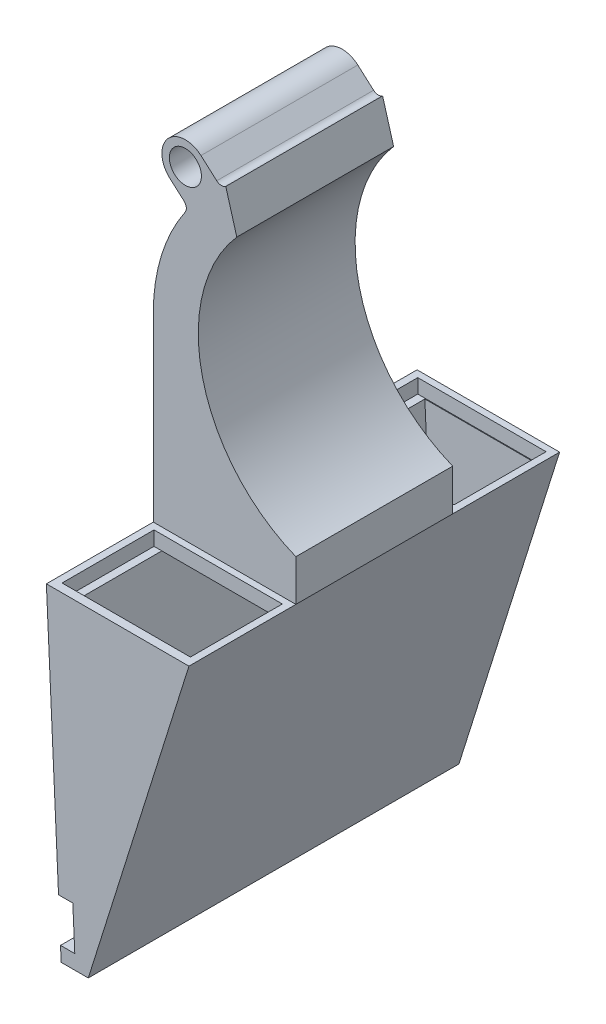
SolidWorks part; units mm, degrees
ref_plane "Front Plane" through (0, 0, 0) normal (0, 0, 1) x (1, 0, 0)
ref_plane "Top Plane" through (0, 0, 0) normal (0, 1, 0) x (1, 0, 0)
ref_plane "Right Plane" through (0, 0, 0) normal (1, 0, 0) x (0, 0, -1)
sketch "Sketch4" plane through (0, -25.4, 0) normal (0, -1, 0) x (1, 0, 0)
  line L1 (-8.5, -1.2) -> (-26.5, -1.2)
  line L2 (-8.5, -1.2) -> (-8.5, -14.1)
  line L3 (-8.5, -14.1) -> (-26.5, -14.1)
  line L4 (-26.5, -1.2) -> (-26.5, -14.1)
  line L5 (-8.5, -1.2) -> (-26.5, -14.1) construction
  line L6 (-8.5, -14.1) -> (-26.5, -1.2) construction
  line L7 (-26.5, -38.2) -> (-8.5, -38.2)
  line L8 (-26.5, -38.2) -> (-26.5, -51.1)
  line L9 (-26.5, -51.1) -> (-8.5, -51.1)
  line L10 (-8.5, -38.2) -> (-8.5, -51.1)
  line L11 (-26.5, -38.2) -> (-8.5, -51.1) construction
  line L12 (-26.5, -51.1) -> (-8.5, -38.2) construction
  point P4 (-17.5, -7.65)
  point P11 (-17.5, -44.65)
sketch "Sketch2" plane through (0, 0, 0) normal (0, 0, 1) x (1, 0, 0)
  line L0 (-7.5, -25.4) -> (-27.5, -25.4)
  line L1 (-27.5, -25.4) -> (-25.424, -70.3521)
  line L2 (-25.424, -70.3521) -> (-21.624, -70.3521)
  line L3 (-21.624, -70.3521) -> (-7.5, -25.4)
  line L4 (-10.2248, -27.4) -> (-25.4055, -27.4)
  line L5 (-25.4055, -27.4) -> (-23.5151, -68.3329)
  line L6 (-23.5151, -68.3329) -> (-23.086, -68.3329)
  line L7 (-23.086, -68.3329) -> (-10.2248, -27.4)
  line L8 (-23.5151, -68.3329) -> (-25.5173, -68.3329)
  line L9 (-25.5173, -68.3329) -> (-25.7944, -62.3329)
  line L10 (-25.7944, -62.3329) -> (-23.7922, -62.3329)
  line L11 (-21.4047, -86.4829) -> (-21.5662, -82.9866) construction
  point P13 (0, 0)
  line M18 (-27.5, -25.4) -> (-7.5, -25.4)
  dimension "D1" = 2
  dimension "D2" = 2
  dimension "D3" = 3.8
  dimension "D4" = 2
  dimension "D5" = 6
  dimension "D6" = 45
extrude "Boss-Extrude1" add sketch "Sketch2" against normal up to surface (52 mm away) contours L1 L10 L5 L4 L7 L6 L8 L2 L3 M18 region at (-15.0314, -47.7286, 0)
extrude "Boss-Extrude2" add sketch "Sketch2<3>" against normal blind 1 contours L6 L7 L4 L5 region at (-19.6939, -41.4194, 0)
sketch "Sketch2<3>" plane through (0, 0, 0) normal (0, 0, 1) x (1, 0, 0) same geometry as "Sketch2"
extrude "Boss-Extrude3" add sketch "Sketch2<4>" along normal blind 1 from surface contours L6 L7 L4 L5 region at (-19.6939, -41.4194, 0) starting at face at (-21.5868, -50.7636, -52)
sketch "Sketch2<4>" plane through (0, 0, 0) normal (0, 0, 1) x (1, 0, 0) same geometry as "Sketch2"
extrude "Cut-Extrude1" cut sketch "Sketch4" along normal up to surface (2 mm away) up to face at (-17.8152, -27.4, -26)
sketch "Sketch5" plane through (0, 0, -15) normal (0, 0, -1) x (-1, 0, 0)
  line L0 (7.5, -25.4) -> (7.5, -22.9558)
  line L1 (7.5, -25.4) -> (7.5, -22.9558) construction
  line L2 (27.5, -25.4) -> (27.5, 0.0168)
  line L4 (23.2069, 15.7789) -> (25.1853, 17.5272)
  line L5 (18.5989, 20.5146) -> (20.8147, 22.4728)
  line L6 (17.3331, 20.4667) -> (15.788, 15.0809)
  line L7 (7.5, -22.9558) -> (7.5, -19.6032)
  line L8 (7.5, -25.4) -> (27.5, -25.4)
  circle A0 centre (23, 20) radius 3.3
  circle A1 centre (23, 20) radius 2.25
  arc A2 (7.5, -22.9558) -> (4.899, -21.0483) centre (5.5, -22.9558) ccw construction
  arc A3 (27.5, 0) -> (23.0428, 14.4662) centre (1.85, 0.0168) ccw construction
  arc A4 (27.5, 0.0168) -> (23.0428, 14.4662) centre (1.85, 0.0168) ccw
  arc A5 (23.0428, 14.4662) -> (23.2069, 15.7789) centre (23.8691, 15.0296) cw
  arc A7 (17.3331, 20.4667) -> (18.5989, 20.5146) centre (17.9367, 21.2639) ccw
  arc A8 (15.788, 15.0809) -> (7.5, -19.6032) centre (-0.6849, 0.6849) cw
  arc A9 (0.5, -21.1599) -> (14.4268, -15.1339) centre (-0.6849, 0.6849) ccw construction
extrude "Boss-Extrude4" add sketch "Sketch5" along normal up to surface (22 mm away) contours L6 A8 L7 L0 L8 L2 A4 A5 L4 A0 L5 A7 | A0 A1 region at (-20.6695, -8.6144, -15) region at (-20.5972, 17.8766, -15)
